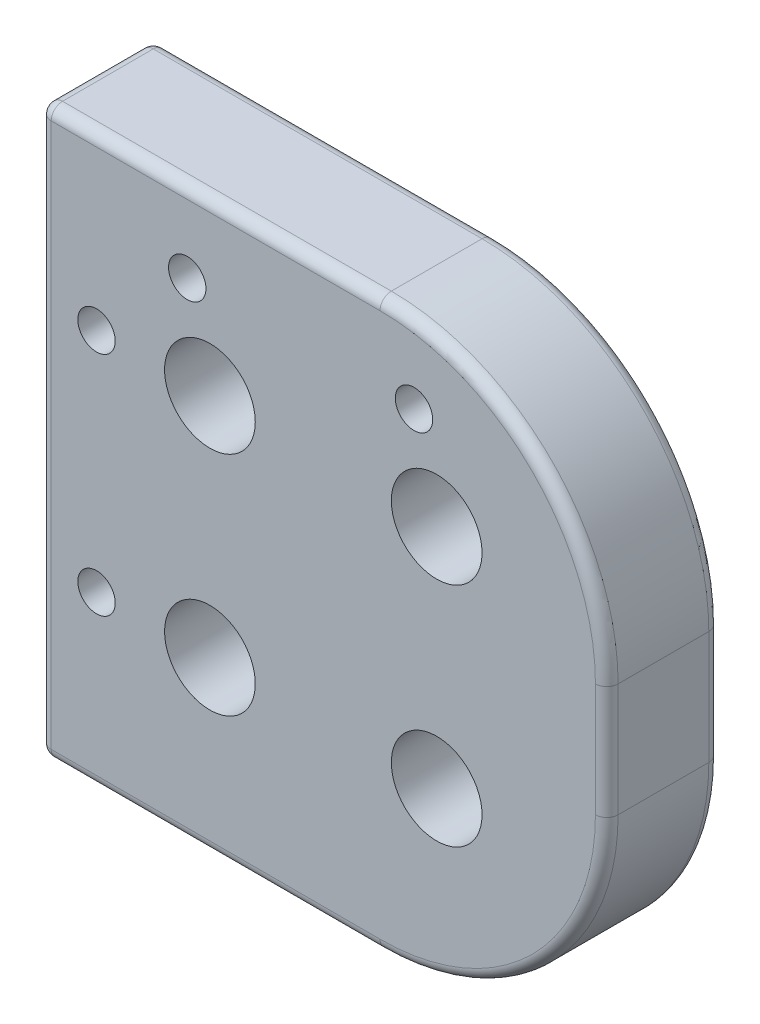
SolidWorks part; units mm, degrees
ref_plane "前视基准面" through (0, 0, 0) normal (0, 0, 1) x (1, 0, 0)
ref_plane "上视基准面" through (0, 0, 0) normal (0, 1, 0) x (1, 0, 0)
ref_plane "右视基准面" through (0, 0, 0) normal (1, 0, 0) x (0, 0, -1)
sketch "草图1" plane through (0, 0, 0) normal (0, 0, 1) x (1, 0, 0)
  line L1 (-25, -25) -> (25, -25) construction
  line L2 (-25, -25) -> (-25, 25)
  line L3 (-25, 25) -> (25, 25) construction
  line L4 (25, -25) -> (25, 25) construction
  line L5 (-25, -25) -> (25, 25) construction
  line L6 (-25, 25) -> (25, -25) construction
  line L7 (-25, 25) -> (25, 25)
  line L8 (-25, -25) -> (25, -25)
  line L9 (25, -25) -> (25, 25)
  point P0 (0, 0)
  dimension "D1" = 50
  dimension "D2" = 50
extrude "凸台-拉伸1" add sketch "草图1" along normal blind 10
sketch "草图2" plane through (0, 0, 10) normal (0, 0, 1) x (1, 0, 0)
  line L0 (0, 0) -> (50000, 0) construction
  line L7 (-10, -10) -> (-10, 10) construction
  line L8 (-10, 10) -> (15, 10) construction
  line L9 (15, -10) -> (15, 10) construction
  line L10 (-10, -10) -> (15, 10) construction
  line L11 (-10, 10) -> (15, -10) construction
  line L12 (2.5, 0) -> (2.5, 50000) construction
  line L13 (-10, -10) -> (15, -10) construction
  circle A4 centre (-10, 10) radius 1.6
  circle A5 centre (15, 10) radius 1.6
  circle A6 centre (15, -10) radius 1.6
  circle A7 centre (-10, -10) radius 1.6
  point P0 (2.5, 0)
  dimension "D3" = 2.5
  dimension "D4" = 3.2
  dimension "D1" = 20
  dimension "D2" = 25
extrude "切除-拉伸1" [suppressed] cut sketch "草图2" against normal through all
fillet "圆角1" radius 20 2 edges at (25, -25, 5) (25, 25, 5)
fillet "圆角2" radius 1 14 edges at (-10, -25, 0) (-10, -25, 10) (-25, 0, 0) (-10, 25, 0) (-10, 25, 10) (-25, 0, 10) (-25, -25, 5) (-25, 25, 5) (19.1421, -19.1421, 0) (25, 0, 0) (19.1421, 19.1421, 0) (19.1421, -19.1421, 10) (25, 0, 10) (19.1421, 19.1421, 10)
sketch "草图3" plane through (0, 0, 10) normal (0, 0, 1) x (1, 0, 0)
  line L0 (0, 30.5262) -> (0, -32.5462) construction
  line L1 (-34.1369, 0) -> (41.2066, 0) construction
  circle A0 centre (-10, 10) radius 4
  circle A1 centre (10, 10) radius 4
  circle A2 centre (10, -10) radius 4
  circle A3 centre (-10, -10) radius 4
  dimension "D1" = 8
  dimension "D2" = 10
  dimension "D3" = 10
extrude "切除-拉伸2" cut sketch "草图3" against normal blind 10
sketch "草图4" plane through (0, 0, 10) normal (0, 0, 1) x (1, 0, 0)
  line L1 (-10, 10) -> (10, 10) construction
  line L2 (-10, -10) -> (10, -10) construction
  circle A0 centre (-20, -10) radius 1.65
  circle A1 centre (-10, -10) radius 4 construction
  circle A2 centre (-20, 10) radius 1.65
  circle A4 centre (-10, 10) radius 4 construction
  circle A5 centre (-12, 18) radius 1.65
  circle A6 centre (8, 18) radius 1.65
  dimension "D1" = 3.3
  dimension "D2" = 10
  dimension "D3" = 3.3
  dimension "D4" = 10
  dimension "D5" = 3.3
  dimension "D6" = 3.3
  dimension "D7" = 20
  dimension "D8" = 2
  dimension "D9" = 8
extrude "切除-拉伸3" cut sketch "草图4" against normal blind 10
equation "\"3。2\"=3.16193"
